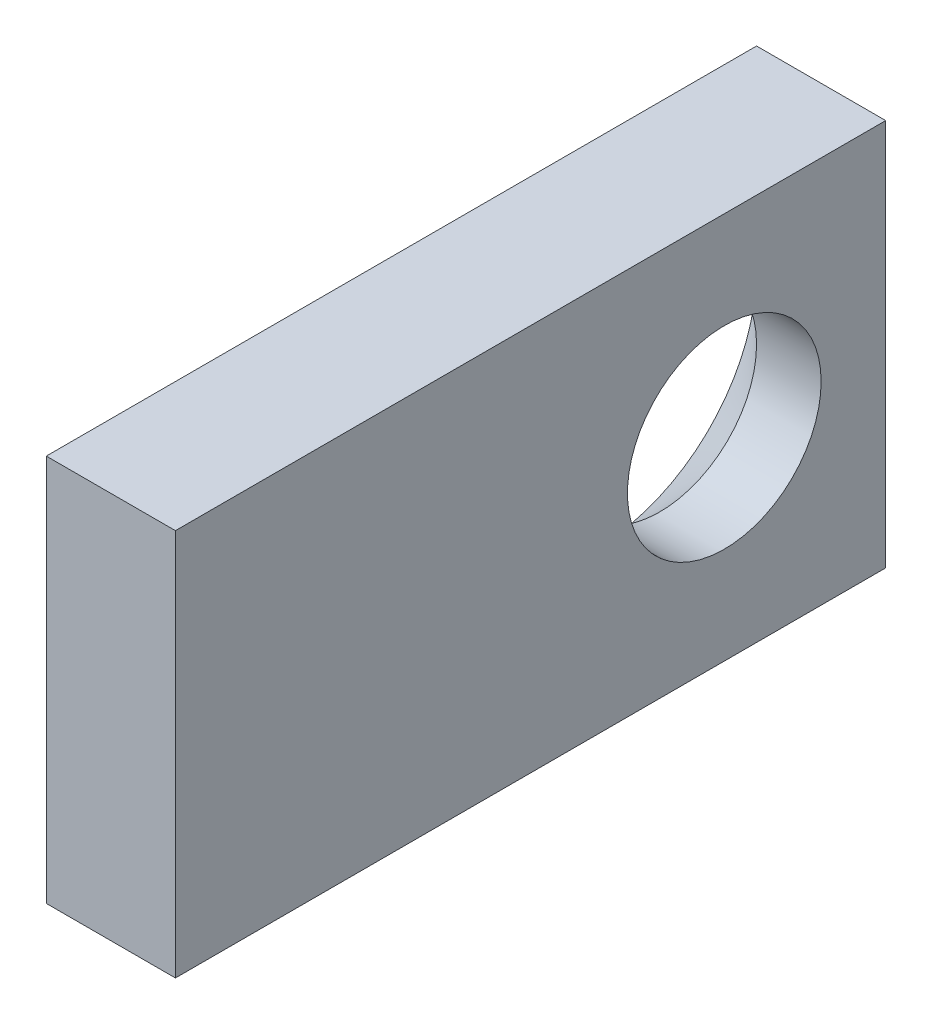
SolidWorks part; units mm, degrees
ref_plane "Спереди" through (0, 0, 0) normal (0, 0, 1) x (1, 0, 0)
ref_plane "Сверху" through (0, 0, 0) normal (0, 1, 0) x (1, 0, 0)
ref_plane "Справа" through (0, 0, 0) normal (1, 0, 0) x (0, 0, -1)
sketch "Эскиз1" plane through (0, 0, 0) normal (1, 0, 0) x (0, 0, -1)
  line L0 (0, 3) -> (-2.5, 3)
  line L1 (0, 0) -> (-11, 0)
  line L2 (0, 0) -> (0, 6)
  line L3 (0, 6) -> (-11, 6)
  line L4 (-11, 0) -> (-11, 6)
  circle A0 centre (-2.5, 3) radius 1.5
  dimension "D3" = 3
  dimension "D4" = 2.5
  dimension "D1" = 11
  dimension "D2" = 6
extrude "Бобышка-Вытянуть1" add sketch "Эскиз1" along normal blind 2 contours A0 L2 L3 L4 L1 region at (0, 3, 5.8598)
chamfer "Фаска1" distance 1 angle 45 1 edges at (0, 3, 1)
